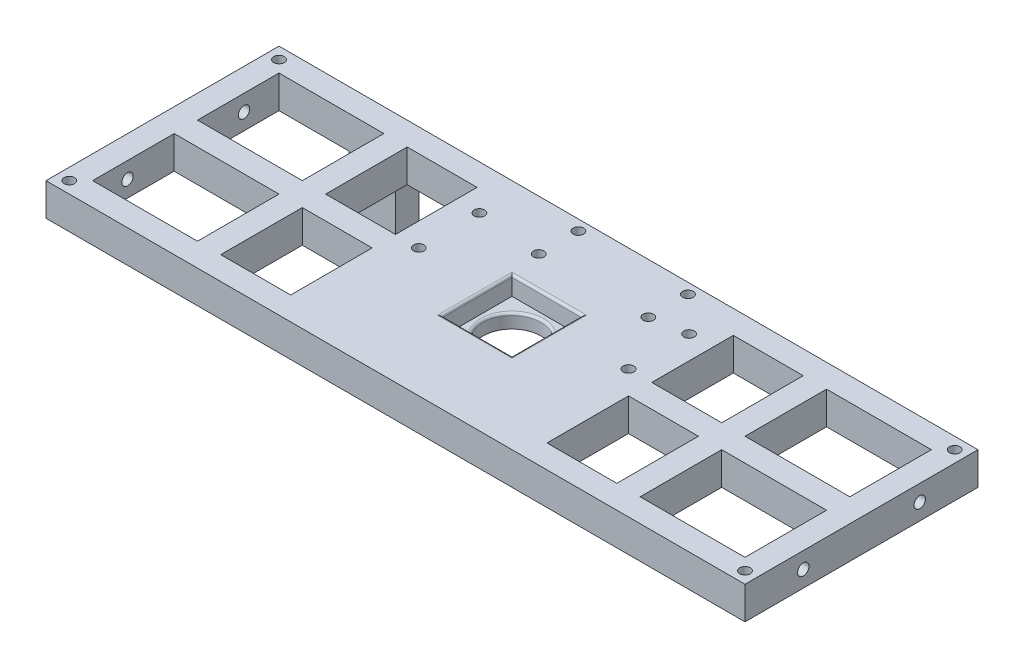
SolidWorks part; units mm, degrees
ref_plane "前视基准面" through (0, 0, 0) normal (0, 0, 1) x (1, 0, 0)
ref_plane "上视基准面" through (0, 0, 0) normal (0, 1, 0) x (1, 0, 0)
ref_plane "右视基准面" through (0, 0, 0) normal (1, 0, 0) x (0, 0, -1)
sketch "草图1" plane through (0, 0, 0) normal (0, 1, 0) x (1, 0, 0)
  line L1 (0, 0) -> (-300, 0)
  line L2 (0, 0) -> (0, 100)
  line L3 (0, 100) -> (-300, 100)
  line L4 (-300, 0) -> (-300, 100)
  dimension "D1" = 300
  dimension "D2" = 100
extrude "凸台-拉伸1" add sketch "草图1" along normal blind 16
sketch "草图2" plane through (0, 16, 0) normal (0, 1, 0) x (1, 0, 0)
  line L0 (-150, 100) -> (-150, 50) construction
  line L1 (0, 100) -> (-300, 100) construction
  line L2 (-300, 50) -> (-150, 50) construction
  line L3 (-300, 100) -> (-300, 0) construction
  line L5 (-165, 65) -> (-135, 65)
  line L6 (-165, 65) -> (-165, 35)
  line L7 (-165, 35) -> (-135, 35)
  line L8 (-135, 65) -> (-135, 35)
  line L9 (-165, 65) -> (-135, 35) construction
  line L10 (-165, 35) -> (-135, 65) construction
  dimension "D1" = 50
  dimension "D2" = 30
  dimension "D3" = 30
extrude "切除-拉伸1" cut sketch "草图2" against normal blind 8
sketch "草图3" plane through (0, 8, 0) normal (0, 1, 0) x (1, 0, 0)
  line L0 (-135, 65) -> (-165, 65) construction
  line L1 (-135, 35) -> (-135, 65) construction
  circle A0 centre (-150, 50) radius 12.5
  dimension "D3" = 25
  dimension "D1" = 15
  dimension "D2" = 15
extrude "切除-拉伸2" cut sketch "草图3" against normal blind 14
sketch "草图4" plane through (0, 16, 0) normal (0, 1, 0) x (1, 0, 0)
  line L0 (-165, 65) -> (-165, 35) construction
  line L1 (-295, 90) -> (-245, 90)
  line L2 (-295, 90) -> (-295, 55)
  line L3 (-295, 55) -> (-245, 55)
  line L4 (-245, 90) -> (-245, 55)
  line L5 (-295, 45) -> (-245, 45)
  line L6 (-295, 45) -> (-295, 10)
  line L7 (-295, 10) -> (-245, 10)
  line L8 (-245, 45) -> (-245, 10)
  line L9 (-235, 90) -> (-185, 90)
  line L10 (-235, 90) -> (-235, 55)
  line L11 (-235, 55) -> (-185, 55)
  line L12 (-185, 90) -> (-185, 55)
  line L13 (-235, 45) -> (-185, 45)
  line L14 (-235, 45) -> (-235, 10)
  line L15 (-235, 10) -> (-185, 10)
  line L16 (-185, 45) -> (-185, 10)
  line L17 (0, 100) -> (-300, 100) construction
  line L18 (-300, 0) -> (0, 0) construction
  line L19 (-300, 100) -> (-300, 0) construction
  line L20 (-150, 100) -> (-150, 73.2626) construction
  line L21 (-5, 10) -> (-55, 10)
  line L22 (-55, 45) -> (-55, 10)
  line L23 (-5, 45) -> (-55, 45)
  line L24 (-5, 45) -> (-5, 10)
  line L25 (-65, 10) -> (-115, 10)
  line L26 (-115, 45) -> (-115, 10)
  line L27 (-65, 45) -> (-115, 45)
  line L28 (-65, 45) -> (-65, 10)
  line L29 (-65, 55) -> (-115, 55)
  line L30 (-115, 90) -> (-115, 55)
  line L31 (-65, 90) -> (-115, 90)
  line L32 (-65, 90) -> (-65, 55)
  line L33 (-5, 55) -> (-55, 55)
  line L34 (-55, 90) -> (-55, 55)
  line L35 (-5, 90) -> (-55, 90)
  line L36 (-5, 90) -> (-5, 55)
  dimension "D1" = 20
  dimension "D2" = 20
  dimension "D3" = 10
  dimension "D4" = 10
  dimension "D5" = 10
  dimension "D6" = 35
  dimension "D7" = 10
  dimension "D8" = 10
  dimension "D9" = 5
  dimension "D10" = 5
  dimension "D11" = 35
  dimension "D12" = 35
  dimension "D13" = 50
  dimension "D14" = 50
  dimension "D15" = 50
  dimension "D16" = 50
extrude "切除-拉伸3" cut sketch "草图4" against normal up to next
sketch "草图7" plane through (-185, 0, 0) normal (-1, 0, 0) x (0, 0, 1)
  line L0 (-45, 0) -> (-10, 0) construction
  line L1 (-10, 0) -> (-10, 16) construction
  line L2 (-10, 16) -> (-45, 16) construction
  line L3 (-45, 16) -> (-45, 0) construction
  line L4 (-90, 0) -> (-55, 0) construction
  line L5 (-55, 0) -> (-55, 16) construction
  line L6 (-55, 16) -> (-90, 16) construction
  line L7 (-90, 16) -> (-90, 0) construction
  line L8 (-45, 0) -> (-10, 0)
  line L9 (-10, 0) -> (-10, 16)
  line L10 (-10, 16) -> (-45, 16)
  line L11 (-45, 16) -> (-45, 0)
  line L12 (-90, 0) -> (-55, 0)
  line L13 (-55, 0) -> (-55, 16)
  line L14 (-55, 16) -> (-90, 16)
  line L15 (-90, 16) -> (-90, 0)
extrude "凸台-拉伸2" add sketch "草图7" along normal blind 20
sketch "草图8" plane through (-115, 0, 0) normal (1, 0, 0) x (0, 0, -1)
  line L0 (10, 0) -> (45, 0) construction
  line L1 (45, 0) -> (45, 16) construction
  line L2 (45, 16) -> (10, 16) construction
  line L3 (10, 16) -> (10, 0) construction
  line L4 (55, 0) -> (90, 0) construction
  line L5 (90, 0) -> (90, 16) construction
  line L6 (90, 16) -> (55, 16) construction
  line L7 (55, 16) -> (55, 0) construction
  line L8 (10, 0) -> (45, 0)
  line L9 (45, 0) -> (45, 16)
  line L10 (45, 16) -> (10, 16)
  line L11 (10, 16) -> (10, 0)
  line L12 (55, 0) -> (90, 0)
  line L13 (90, 0) -> (90, 16)
  line L14 (90, 16) -> (55, 16)
  line L15 (55, 16) -> (55, 0)
extrude "凸台-拉伸3" add sketch "草图8" along normal blind 20
sketch "草图9" plane through (0, 0, 0) normal (0, -1, 0) x (1, 0, 0)
  line L5 (-295, -90) -> (-245, -90) construction
  line L10 (-260, -90) -> (-240, -90)
  line L20 (-260, -90) -> (-260, -100)
  line L21 (-260, -100) -> (-240, -100)
  line L22 (-240, -90) -> (-240, -100)
  line L23 (0, -100) -> (-300, -100) construction
  line L24 (-300, -100) -> (-300, 0) construction
  dimension "D3" = 20
  dimension "D4" = 40
extrude "凸台-拉伸4" add sketch "草图9" along normal blind 25
fillet "圆角1" radius 1 1 edges at (-150, 8, -37.5)
fillet "圆角2" radius 1 4 edges at (-135, 16, -50) (-150, 16, -65) (-150, 16, -35) (-165, 16, -50)
sketch "草图13" plane through (-5, 0, 0) normal (-1, 0, 0) x (0, 0, 1)
  line L0 (-90, 0) -> (-55, 0) construction
  line L1 (-55, 0) -> (-55, 16) construction
  line L2 (-55, 16) -> (-90, 16) construction
  line L3 (-90, 16) -> (-90, 0) construction
  line L4 (-45, 0) -> (-10, 0) construction
  line L5 (-10, 0) -> (-10, 16) construction
  line L6 (-10, 16) -> (-45, 16) construction
  line L7 (-45, 16) -> (-45, 0) construction
  line L8 (-90, 0) -> (-55, 0)
  line L9 (-55, 0) -> (-55, 16)
  line L10 (-55, 16) -> (-90, 16)
  line L11 (-90, 16) -> (-90, 0)
  line L12 (-45, 0) -> (-10, 0)
  line L13 (-10, 0) -> (-10, 16)
  line L14 (-10, 16) -> (-45, 16)
  line L15 (-45, 16) -> (-45, 0)
extrude "凸台-拉伸6" add sketch "草图13" along normal blind 4
sketch "草图14" plane through (-295, 0, 0) normal (1, 0, 0) x (0, 0, -1)
  line L0 (55, 0) -> (90, 0) construction
  line L1 (90, 0) -> (90, 16) construction
  line L2 (90, 16) -> (55, 16) construction
  line L3 (55, 16) -> (55, 0) construction
  line L4 (10, 0) -> (45, 0) construction
  line L5 (45, 0) -> (45, 16) construction
  line L6 (45, 16) -> (10, 16) construction
  line L7 (10, 16) -> (10, 0) construction
  line L8 (55, 0) -> (90, 0)
  line L9 (90, 0) -> (90, 16)
  line L10 (90, 16) -> (55, 16)
  line L11 (55, 16) -> (55, 0)
  line L12 (10, 0) -> (45, 0)
  line L13 (45, 0) -> (45, 16)
  line L14 (45, 16) -> (10, 16)
  line L15 (10, 16) -> (10, 0)
extrude "凸台-拉伸7" add sketch "草图14" along normal blind 4
sketch "草图17" plane through (-291, 0, 0) normal (1, 0, 0) x (0, 0, -1)
  line L0 (10, 16) -> (10, 0) construction
  line L1 (10, 0) -> (45, 0) construction
  line L2 (45, 0) -> (45, 16) construction
  line L3 (45, 16) -> (10, 16) construction
  line L4 (55, 16) -> (55, 0) construction
  line L5 (55, 0) -> (90, 0) construction
  line L6 (90, 0) -> (90, 16) construction
  line L7 (90, 16) -> (55, 16) construction
  line L8 (10, 16) -> (10, 0)
  line L9 (10, 0) -> (45, 0)
  line L10 (45, 0) -> (45, 16)
  line L11 (45, 16) -> (10, 16)
  line L12 (55, 16) -> (55, 0)
  line L13 (55, 0) -> (90, 0)
  line L14 (90, 0) -> (90, 16)
  line L15 (90, 16) -> (55, 16)
extrude "凸台-拉伸8" add sketch "草图17" along normal blind 1
sketch "草图18" plane through (-9, 0, 0) normal (-1, 0, 0) x (0, 0, 1)
  line L0 (-45, 16) -> (-45, 0) construction
  line L1 (-45, 0) -> (-10, 0) construction
  line L2 (-10, 0) -> (-10, 16) construction
  line L3 (-10, 16) -> (-45, 16) construction
  line L4 (-90, 16) -> (-90, 0) construction
  line L5 (-90, 0) -> (-55, 0) construction
  line L6 (-55, 0) -> (-55, 16) construction
  line L7 (-55, 16) -> (-90, 16) construction
  line L8 (-45, 16) -> (-45, 0)
  line L9 (-45, 0) -> (-10, 0)
  line L10 (-10, 0) -> (-10, 16)
  line L11 (-10, 16) -> (-45, 16)
  line L12 (-90, 16) -> (-90, 0)
  line L13 (-90, 0) -> (-55, 0)
  line L14 (-55, 0) -> (-55, 16)
  line L15 (-55, 16) -> (-90, 16)
extrude "凸台-拉伸9" add sketch "草图18" along normal blind 1
sketch "草图19" plane through (0, 16, 0) normal (0, 1, 0) x (1, 0, 0)
  line L0 (-300, 100) -> (-295, 100) construction
  line L1 (0, 100) -> (-300, 100) construction
  line L2 (-295, 100) -> (-295, 95) construction
  line L3 (-150, 100) -> (-150, 83.4567) construction
  line L4 (-300, 50) -> (-202.8605, 50) construction
  line L5 (-300, 100) -> (-300, 0) construction
  line L6 (-150, 0) -> (-150, 22.48) construction
  line L7 (-300, 0) -> (0, 0) construction
  line L8 (-5, 100) -> (-5, 95) construction
  line L9 (0, 100) -> (-5, 100) construction
  circle A0 centre (-295, 95) radius 2.25
  circle A1 centre (-295, 5) radius 2.25
  circle A4 centre (-5, 5) radius 2.25
  circle A5 centre (-5, 95) radius 2.25
  dimension "D3" = 4.5
  dimension "D1" = 5
  dimension "D2" = 5
extrude "切除-拉伸8" cut sketch "草图19" against normal blind 5
sketch "草图24" [suppressed] plane through (0, 16, 0) normal (0, 1, 0) x (1, 0, 0)
  circle A0 centre (-195, 81) radius 2.25
  circle A1 centre (-205, 54.9815) radius 2.25
  circle A2 centre (-105, 81) radius 2.25
  circle A3 centre (-115, 54.9815) radius 2.25
  dimension "D1" = 4.5
  dimension "D2" = 4.5
  dimension "D3" = 4.5
  dimension "D4" = 4.5
extrude "切除-拉伸13" [suppressed] cut sketch "草图24" against normal blind 5
sketch "草图26" plane through (0, 0, 0) normal (0, -1, 0) x (1, 0, 0)
  line L12 (-260, -90) -> (-290, -90)
  line L13 (-290, -90) -> (-290, -55)
  line L14 (-290, -55) -> (-245, -55)
  line L15 (-245, -55) -> (-245, -90)
  line L16 (-245, -90) -> (-240, -90)
  line L17 (-240, -90) -> (-240, -100)
  line L18 (-240, -100) -> (0, -100)
  line L19 (0, -100) -> (0, 0)
  line L20 (0, 0) -> (-300, 0)
  line L21 (-300, 0) -> (-300, -100)
  line L22 (-300, -100) -> (-260, -100)
  line L23 (-260, -100) -> (-260, -90)
  line L24 (-260, -90) -> (-290, -90)
  line L25 (-290, -90) -> (-290, -55)
  line L26 (-290, -55) -> (-245, -55)
  line L27 (-245, -55) -> (-245, -90)
  line L28 (-245, -90) -> (-240, -90)
  line L29 (-240, -90) -> (-240, -100)
  line L30 (-240, -100) -> (0, -100)
  line L31 (0, -100) -> (0, 0)
  line L32 (0, 0) -> (-300, 0)
  line L33 (-300, 0) -> (-300, -100)
  line L34 (-300, -100) -> (-260, -100)
  line L35 (-260, -100) -> (-260, -90)
  dimension "D1" = 0
extrude "切除-拉伸15" cut sketch "草图26" against normal blind 2
sketch "草图28" plane through (0, 16, 0) normal (0, 1, 0) x (1, 0, 0)
  line L0 (-205, 55) -> (-205, 90) construction
  line L1 (0, 100) -> (-300, 100) construction
  line L2 (-95, 90) -> (-95, 55) construction
  circle A8 centre (-105.0028, 55) radius 2.25
  circle A9 centre (-105, 81) radius 2.25
  circle A10 centre (-120, 78.5) radius 2.25
  circle A11 centre (-120, 95.5) radius 2.25
  circle A12 centre (-167.0001, 78.5) radius 2.25
  circle A13 centre (-167.0001, 95.5) radius 2.25
  circle A14 centre (-195, 55) radius 2.25
  circle A15 centre (-195, 81) radius 2.25
  dimension "D1" = 10
  dimension "D2" = 10
  dimension "D3" = 26
  dimension "D4" = 19
  dimension "D5" = 4.5
  dimension "D6" = 4.5
  dimension "D7" = 17
  dimension "D8" = 4.5
  dimension "D9" = 4.5
  dimension "D10" = 17
  dimension "D11" = 47.0001
  dimension "D12" = 47.0001
  dimension "D13" = 4.5
  dimension "D14" = 4.5
  dimension "D15" = 4.5
  dimension "D16" = 4.5
  dimension "D17" = 25
  dimension "D18" = 25
  dimension "D19" = 10
  dimension "D20" = 10.0028
  dimension "D21" = 26
  dimension "D22" = 19
  dimension "D23" = 4.5
  dimension "D24" = 4.5
extrude "切除-拉伸18" cut sketch "草图28" against normal blind 5
sketch "草图30" plane through (0, 11, 0) normal (0, 1, 0) x (1, 0, 0)
  circle A2 centre (-195, 81) radius 1.5
  circle A3 centre (-195, 55) radius 1.5
  circle A4 centre (-167.0001, 95.5) radius 1.5
  circle A5 centre (-167.0001, 78.5) radius 1.5
  circle A6 centre (-120, 95.5) radius 1.5
  circle A7 centre (-120, 78.5) radius 1.5
  circle A8 centre (-105, 81) radius 1.5
  circle A9 centre (-105.0028, 55) radius 1.5
  dimension "D1" = 3
extrude "切除-拉伸20" cut sketch "草图30" against normal blind 4
sketch "草图33" plane through (-300, 0, 0) normal (-1, 0, 0) x (0, 0, 1)
  line L0 (-100, 16) -> (0, 16) construction
  line L3 (-100, 16) -> (-100, 2) construction
  line L4 (0, 16) -> (0, 2) construction
  circle A0 centre (-75, 9) radius 2.45
  circle A1 centre (-25, 9) radius 2.45
  dimension "D1" = 7
  dimension "D2" = 7
  dimension "D3" = 4.9
  dimension "D4" = 4.9
  dimension "D5" = 25
  dimension "D6" = 25
extrude "切除-拉伸22" cut sketch "草图33" against normal blind 13.2
sketch "草图34" plane through (0, 0, 0) normal (1, 0, 0) x (0, 0, -1)
  circle A0 centre (75, 9) radius 2.45 construction
  circle A1 centre (25, 9) radius 2.45 construction
  circle A2 centre (75, 9) radius 2.45
  circle A3 centre (25, 9) radius 2.45
extrude "切除-拉伸23" cut sketch "草图34" against normal blind 13.2
